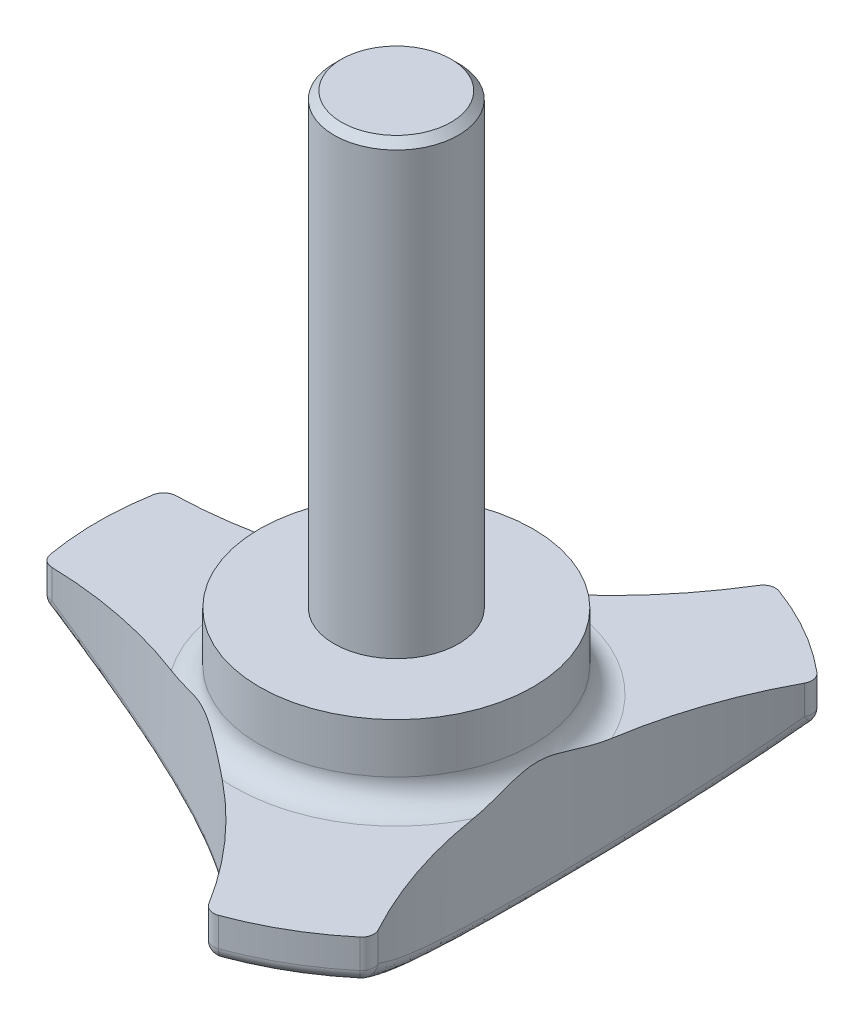
SolidWorks part; units mm, degrees
ref_plane "Płaszczyzna przednia" through (0, 0, 0) normal (0, 0, 1) x (1, 0, 0)
ref_plane "Płaszczyzna górna" through (0, 0, 0) normal (0, 1, 0) x (1, 0, 0)
ref_plane "Płaszczyzna prawa" through (0, 0, 0) normal (1, 0, 0) x (0, 0, -1)
sketch "Szkic1" plane through (0, 0, 0) normal (0, 1, 0) x (1, 0, 0)
  line L0 (-28.4575, 0) -> (34.017, 0) construction
  circle A0 centre (0, 0) radius 12
  dimension "D1" = 24
extrude "Dodanie-wyciągnięcie1" add sketch "Szkic1" along normal blind 5
sketch "Szkic2" plane through (0, 5, 0) normal (0, 1, 0) x (1, 0, 0)
  line L0 (-16.9313, 0) -> (22.3018, 0) construction
  circle A0 centre (0, 0) radius 12 construction
  arc A1 (-11.7367, -2.5001) -> (3.733, -11.4046) centre (0, 0) ccw
  arc A2 (-11.7367, -2.5001) -> (3.733, -11.4046) centre (-11.8, -20.5) cw
  dimension "D1" = 18
  dimension "D2" = 20.5
  dimension "D3" = 11.8
extrude "Wytnij-wyciągnięcie1" cut sketch "Szkic2" against normal blind 5 contours A2 A1
pattern_circular "Szyk kołowy1" count 3 over 360 about axis through (0, 5, 0) along (0, 1, 0) of "Wytnij-wyciągnięcie1"
sketch "Szkic3" plane through (0, 0, 0) normal (0, 0, 1) x (1, 0, 0)
  line L0 (0, -5.3383) -> (0, 25.9641) construction
  line L1 (0, 0) -> (0, -1)
  line L2 (0, -1) -> (-12, -1)
  line L3 (-12, 3.5609) -> (-12, -1)
  line L4 (-12, 5) -> (-12, 0) construction
  arc A0 (0, 0) -> (-12, 3.5609) centre (0, 22) cw
  dimension "D1" = 22
  dimension "D2" = 12
  dimension "D3" = 1
revolve "Wycięcie-obrót2" cut sketch "Szkic3" angle 360 about L0
fillet "Zaokrąglenie1" radius 0.5 12 edges at (6.0136, 3.5609, 10.3845) (-12, 3.5609, 0.0157) (5.9864, 3.5609, -10.4001) (3.7032, 4.2805, -11.4143) (8.0102, 4.2805, -8.9352) (8.0335, 4.2805, 8.9142) (3.733, 4.2805, 11.4046) (-11.7367, 4.2805, 2.5001) (-11.7432, 4.2805, -2.4694) (-2.0457, 0.7652, -5.3759) (5.6785, 0.7652, 0.9163) (-3.6328, 0.7652, 4.4595)
sketch "Szkic4" plane through (0, 5, 0) normal (0, 1, 0) x (1, 0, 0)
  circle A0 centre (0, 0) radius 5.5
  dimension "D1" = 11
extrude "Dodanie-wyciągnięcie2" add sketch "Szkic4" along normal blind 3
sketch "Szkic5" plane through (0, 8, 0) normal (0, 1, 0) x (1, 0, 0)
  circle A0 centre (0, 0) radius 2.5
  dimension "D1" = 5
extrude "Dodanie-wyciągnięcie3" add sketch "Szkic5" along normal blind 18
fillet "Zaokrąglenie2" radius 1 1 edges at (0, 5, 5.5)
chamfer "Sfazowanie1" distance 0.3 angle 45 1 edges at (0, 26, 2.5)
